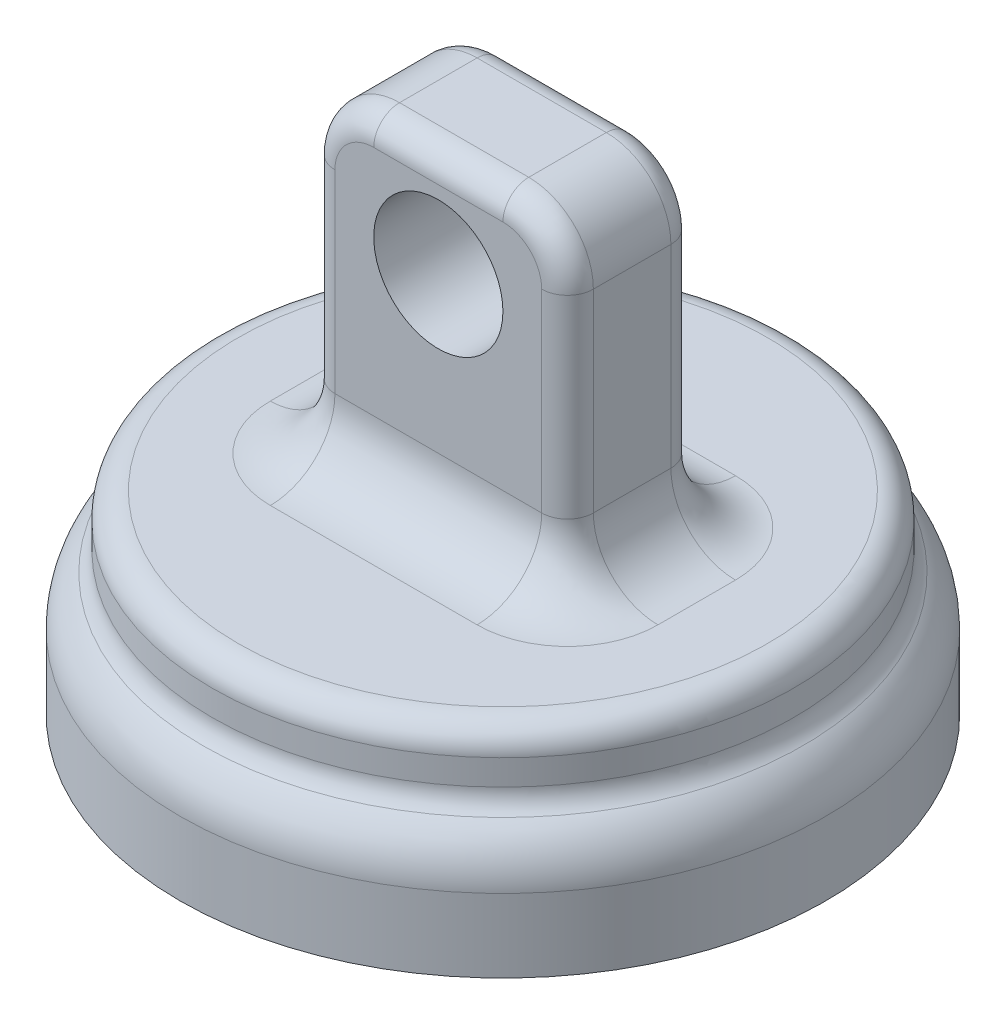
SolidWorks part; units mm, degrees
ref_plane "Front Plane" through (0, 0, 0) normal (0, 0, 1) x (1, 0, 0)
ref_plane "Top Plane" through (0, 0, 0) normal (0, 1, 0) x (1, 0, 0)
ref_plane "Right Plane" through (0, 0, 0) normal (1, 0, 0) x (0, 0, -1)
sketch "Sketch1" plane through (0, 0, 0) normal (0, 1, 0) x (1, 0, 0)
  circle A0 centre (0, 0) radius 25
  dimension "D1" = 50
extrude "Boss-Extrude1" add sketch "Sketch1" along normal blind 10
sketch "Sketch2" plane through (0, 10, 0) normal (0, 1, 0) x (1, 0, 0)
  circle A0 centre (0, 0) radius 22.5
  dimension "D1" = 45
extrude "Boss-Extrude2" add sketch "Sketch2" along normal blind 5
fillet "Fillet3" radius 5 1 edges at (0, 10, 25)
fillet "Fillet4" radius 2 1 edges at (0, 15, 22.5)
fillet "Fillet5" radius 2 1 edges at (0, 10, 22.5)
sketch "Sketch3" plane through (0, 0, 0) normal (0, 0, 1) x (1, 0, 0)
  line L0 (0, 0) -> (0, 32) construction
  line L1 (20.5, 15) -> (-20.5, 15) construction
  line L2 (20.5, 15) -> (-20.5, 15) construction
  line L4 (-10, 15) -> (10, 15)
  line L5 (-10, 15) -> (-10, 35)
  line L6 (-5, 40) -> (5, 40)
  line L7 (10, 15) -> (10, 35)
  arc A0 (5, 40) -> (10, 35) centre (5, 35) cw
  arc A1 (-10, 35) -> (-5, 40) centre (-5, 35) cw
  circle A2 centre (0, 32) radius 5
  point P9 (0, 15)
  point P12 (10, 40)
  point P15 (-10, 40)
  dimension "D3" = 5
  dimension "D5" = 10
  dimension "D1" = 20
  dimension "D2" = 25
  dimension "D4" = 17
extrude "Boss-Extrude3" add sketch "Sketch3" against normal mid plane 10
fillet "Fillet6" radius 2 5 edges at (10, 25, 5) (8.5355, 38.5355, 5) (-10, 25, 5) (-8.5355, 38.5355, 5) (0, 40, 5)
fillet "Fillet7" radius 2 5 edges at (10, 25, -5) (8.5355, 38.5355, -5) (-10, 25, -5) (-8.5355, 38.5355, -5) (0, 40, -5)
fillet "Fillet8" radius 5 8 edges at (-9.4142, 15, 4.4142) (-10, 15, 0) (-9.4142, 15, -4.4142) (0, 15, -5) (9.4142, 15, -4.4142) (10, 15, 0) (9.4142, 15, 4.4142) (0, 15, 5)
